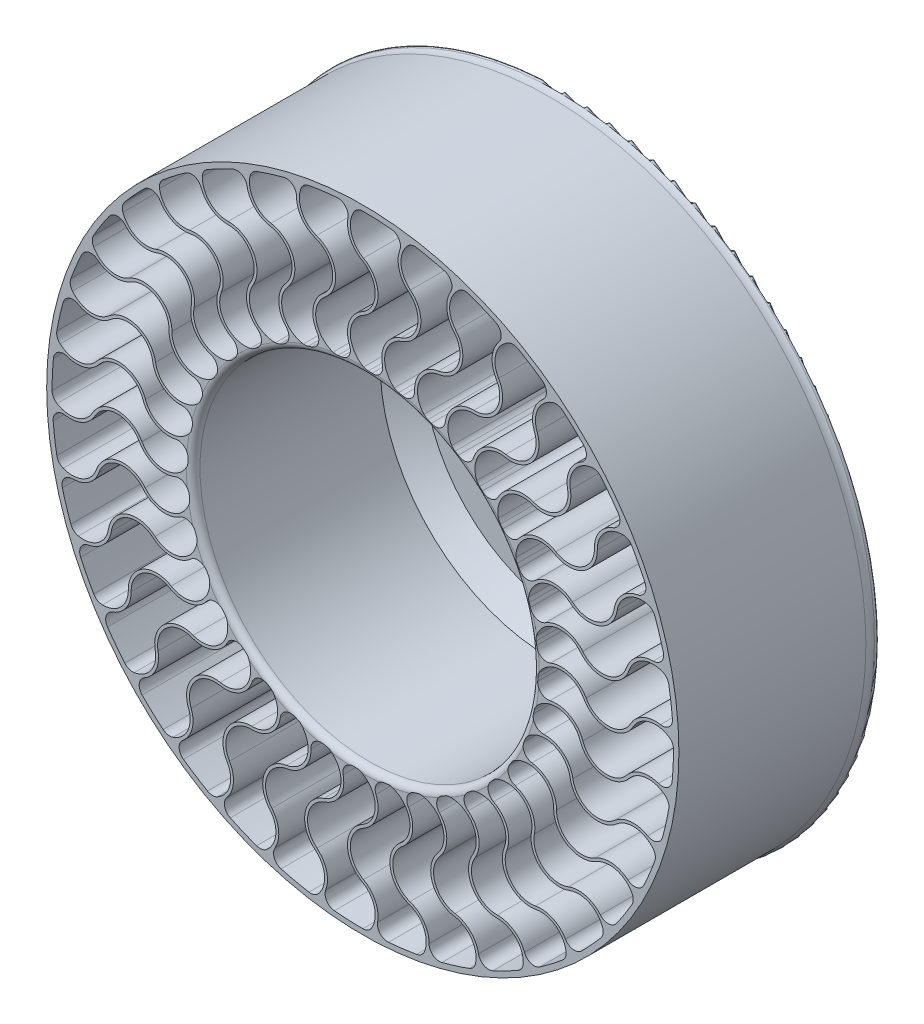
SolidWorks part; units mm, degrees
ref_plane "Front Plane" through (0, 0, 0) normal (0, 0, 1) x (1, 0, 0)
ref_plane "Top Plane" through (0, 0, 0) normal (0, 1, 0) x (1, 0, 0)
ref_plane "Right Plane" through (0, 0, 0) normal (1, 0, 0) x (0, 0, -1)
sketch "Sketch1" plane through (0, 0, 0) normal (0, 0, 1) x (1, 0, 0)
  circle A0 centre (0, 0) radius 24.95
  circle A1 centre (0, 0) radius 25.75
  dimension "D1" = 49.9
  dimension "D2" = 0.8
extrude "Boss-Extrude1" add sketch "Sketch1" along normal blind 27.5
sketch "Sketch2" plane through (0, 0, 27.5) normal (0, 0, 1) x (1, 0, 0)
  line L0 (0, 46.5) -> (0, 25.75) construction
  line L1 (0, 0) -> (0, -25.95) construction
  line L4 (0, 0) -> (0, 25.75) construction
  circle A0 centre (0, 0) radius 25.75 construction
  circle A1 centre (0, 0) radius 46.5 construction
  arc A2 (-0.4056, 46.4982) -> (0.4776, 46.4975) centre (0, 0) cw
  arc A13 (0, 46.5) -> (0, 39.5833) centre (1.9127, 43.0417) ccw construction
  arc A14 (0, 39.5833) -> (0, 32.6667) centre (-1.9127, 36.125) cw construction
  arc A15 (0, 32.6667) -> (0, 25.75) centre (1.9127, 29.2083) ccw construction
  arc A16 (0.4776, 46.4975) -> (0.1016, 39.7671) centre (1.9127, 43.0417) ccw
  arc A17 (0.1016, 39.7671) -> (0.1016, 32.4829) centre (-1.9127, 36.125) cw
  arc A18 (0.1016, 32.4829) -> (0.4951, 25.7452) centre (1.9127, 29.2083) ccw
  arc A19 (-0.4056, 46.4982) -> (-0.1016, 39.3996) centre (1.9127, 43.0417) ccw
  arc A20 (-0.1016, 39.3996) -> (-0.1016, 32.8504) centre (-1.9127, 36.125) cw
  arc A21 (-0.1016, 32.8504) -> (-0.3984, 25.7469) centre (1.9127, 29.2083) ccw
  arc A22 (0.1016, 46.3162) -> (0.1016, 39.7671) centre (1.9127, 43.0417) ccw construction
  arc A23 (-0.1016, 46.6838) -> (-0.1016, 39.3996) centre (1.9127, 43.0417) ccw construction
  arc A24 (0.1016, 32.4829) -> (0.1016, 25.9338) centre (1.9127, 29.2083) ccw construction
  arc A25 (-0.1016, 32.8504) -> (-0.1016, 25.5662) centre (1.9127, 29.2083) ccw construction
  circle A26 centre (0, 0) radius 25.75 construction
  arc A27 (0, 46.5) -> (0, 39.5833) centre (1.9127, 43.0417) ccw construction
  arc A28 (0, 39.5833) -> (0, 32.6667) centre (-1.9127, 36.125) cw construction
  arc A29 (-0.3984, 25.7469) -> (0.4951, 25.7452) centre (0, 0) cw
  arc A30 (0, 32.6667) -> (0, 25.75) centre (1.9127, 29.2083) ccw construction
  arc A31 (0.1016, 39.7671) -> (0.1016, 32.4829) centre (-1.9127, 36.125) cw construction
  dimension "D1" = 93
  dimension "D6" = 0.21
  dimension "D5" = 0.21
extrude "SupportElement" add sketch "Sketch2" against normal through all
sketch "Sketch3" plane through (0, 0, 27.5) normal (0, 0, 1) x (1, 0, 0)
  circle A0 centre (0, 0) radius 46.5
  circle A1 centre (0, 0) radius 45.7
  arc A2 (0.4776, 46.4975) -> (-0.4056, 46.4982) centre (0, 0) ccw construction
  dimension "D1" = 0.8
extrude "WheelRim" add sketch "Sketch3" against normal through all
fillet "SupportFillet" radius 1.5 4 edges at (-1.3052, 45.6814, 13.75) (-0.3984, 25.7469, 13.75) (0.4951, 25.7452, 13.75) (-0.7268, 45.6942, 13.75)
pattern_circular "CirPattern1" count 36 over 360 about axis through (0, 0, 27.5) along (0, 0, -1) of "SupportFillet", "SupportElement"
sketch "Sketch5" plane through (0, 0, 0) normal (0, 1, 0) x (1, 0, 0)
  line L0 (0, 0) -> (0, 31.5884) construction
  line L1 (-24.95, 0) -> (-21.75, 3.1932)
  line L2 (-21.75, 3.1932) -> (0, 3.1932)
  line L3 (0, 3.1932) -> (0, 3.9932)
  line L4 (0, 3.9932) -> (-21.75, 3.9932)
  line L5 (-21.75, 3.9932) -> (-25.75, 0)
  line L6 (-25.75, 0) -> (-24.95, 0)
  line L7 (46.5, 0) -> (-46.5, 0) construction
  line L8 (-21.75, 3.9932) -> (-21.75, 3.1932) construction
  line L9 (46.5, 0) -> (-46.5, 0) construction
  line L11 (-46.5, 0) -> (-45.7, 0)
  arc A0 (-46.5, 0) -> (-46.7679, 1) centre (-48.5, 0) ccw
  arc A1 (-45.7, 0) -> (-46.0751, 1.4) centre (-48.5, 0) ccw
  arc A2 (-46.7679, 1) -> (-46.0751, 1.4) centre (-46.4215, 1.2) cw
  dimension "D3" = 0.8
  dimension "D4" = 2
  dimension "D1" = 51.5
  dimension "D2" = 0.8
  dimension "D5" = 1
  dimension "D6" = 0.8
revolve "Revolve1" add sketch "Sketch5" angle 360 about L0
sketch "Sketch6" plane through (0, 0, -3.1932) normal (0, 0, 1) x (1, 0, 0)
  circle A0 centre (-17, 0) radius 3.5 construction
  circle A1 centre (0, 17) radius 3.5 construction
  circle A2 centre (0, -17) radius 3.5 construction
  circle A3 centre (17, 0) radius 3.5 construction
  circle A4 centre (-17, 0) radius 3.5 construction
  circle A5 centre (0, 17) radius 3.5 construction
  circle A6 centre (0, -17) radius 3.5 construction
  circle A7 centre (17, 0) radius 3.5 construction
  circle A8 centre (-17, 0) radius 3.35
  circle A9 centre (0, -17) radius 3.35
  circle A10 centre (17, 0) radius 3.35
  circle A11 centre (0, 17) radius 3.35
  dimension "D1" = 6.7
extrude "Boss-Extrude2" add sketch "Sketch6" along normal blind 3
sketch "Sketch7" plane through (0, 0, -0.1932) normal (0, 0, 1) x (1, 0, 0)
  circle A0 centre (0, -17) radius 3.35 construction
  circle A1 centre (17, 0) radius 3.35 construction
  circle A2 centre (0, 17) radius 3.35 construction
  circle A3 centre (-17, 0) radius 3.35 construction
  circle A4 centre (0, -17) radius 3.35 construction
  circle A5 centre (17, 0) radius 3.35 construction
  circle A6 centre (0, 17) radius 3.35 construction
  circle A7 centre (-17, 0) radius 3.35 construction
  circle A8 centre (-17, 0) radius 1.45
  circle A9 centre (0, 17) radius 1.45
  circle A10 centre (17, 0) radius 1.45
  circle A11 centre (0, -17) radius 1.45
  dimension "D1" = 2.9
extrude "Cut-Extrude1" cut sketch "Sketch7" against normal through all
fillet "Fillet2" radius 1 5 edges at (24.95, 0, 27.5) (-13.65, 0, -0.1932) (3.35, -17, -0.1932) (3.35, 17, -0.1932) (20.35, 0, -0.1932)
ref_plane "Plane1" through (0, 0, 13.75) normal (0, 0, 1) x (1, 0, 0)
sketch "Sketch8" plane through (0, 0, 0) normal (0, 1, 0) x (1, 0, 0)
  line L1 (108.8481, 29.3599) -> (-95.1042, 29.3599)
  line L2 (108.8481, 29.3599) -> (108.8481, 0)
  line L3 (108.8481, 0) -> (-95.1042, 0)
  line L4 (-95.1042, 29.3599) -> (-95.1042, 0)
  line L5 (46.5, 0) -> (-46.5, 0) construction
extrude "Cut-Extrude2" [suppressed] cut sketch "Sketch8" against normal through all and the other way through all
fillet "Fillet3" [suppressed] radius 10
